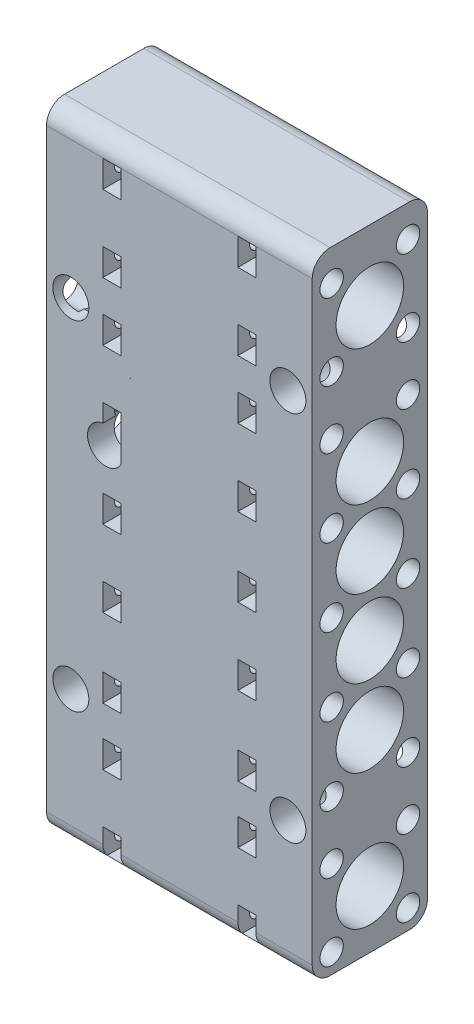
SolidWorks part; units mm, degrees
ref_plane "Plan de face" through (0, 0, 0) normal (0, 0, 1) x (1, 0, 0)
ref_plane "Plan de dessus" through (0, 0, 0) normal (0, 1, 0) x (1, 0, 0)
ref_plane "Plan de droite" through (0, 0, 0) normal (1, 0, 0) x (0, 0, -1)
sketch "Esquisse1" plane through (0, 0, 0) normal (0, 0, 1) x (1, 0, 0)
  line L0 (67.167, -107.583) -> (67.167, -12.4967) construction
  line L1 (67.167, -107.583) -> (118.268, -107.583) construction
  line L2 (67.167, -32.343) -> (118.6716, -32.343) construction
  line L3 (115.367, -14.0613) -> (67.167, -14.0613) construction
  line L4 (115.367, -108.723) -> (115.367, -10.1664) construction
  line L5 (108.4034, -26.123) -> (126.0173, -26.123) construction
  line L6 (91.267, -14.0613) -> (91.267, -17.6404) construction
  line L13 (56.607, -56.8666) -> (109.867, -56.8666) construction
  line L19 (91.267, 2.1061) -> (91.267, -137.8939) construction
  line L20 (61.767, 2.1061) -> (120.767, 2.1061)
  line L21 (61.767, 2.1061) -> (61.767, -137.8939)
  line L22 (61.767, -137.8939) -> (120.767, -137.8939)
  line L23 (120.767, 2.1061) -> (120.767, -137.8939)
  line L24 (61.767, -67.8939) -> (120.767, -67.8939) construction
  circle A0 centre (115.367, -108.723) radius 4
  circle A2 centre (115.367, -26.123) radius 4
  circle A3 centre (74.867, -56.8666) radius 4
  circle A6 centre (67.167, -107.583) radius 4
  circle A7 centre (67.167, -32.343) radius 4
  dimension "D14" = 140
  dimension "D2" = 75.24
  dimension "D3" = 48.2
  dimension "D4" = 6.22
  dimension "D5" = 0
  dimension "D6" = 1.14
  dimension "D15" = 59
extrude "Boss.-Extru.1" add sketch "Esquisse1" along normal blind 25.6
sketch "Esquisse2" plane through (120.767, 0, 0) normal (1, 0, 0) x (0, 0, -1)
  line L0 (-12.8, -125.0284) -> (-21.2853, -133.5136) construction
  line L1 (-12.8, -125.0284) -> (-12.8, -134.7242) construction
  line L2 (-12.8, -95.0284) -> (-21.2853, -103.6294) construction
  line L3 (-12.8, -137.8939) -> (-12.8, 2.1061) construction
  line L4 (-25.6, -137.8939) -> (0, -137.8939) construction
  line L5 (-25.6, 2.1061) -> (0, 2.1061) construction
  line L6 (-12.8, -95.0284) -> (-22.9445, -95.0284) construction
  line L7 (-21.2853, -86.4273) -> (-4.3147, -86.4273) construction
  line L8 (-21.2853, -69.2253) -> (-4.3147, -69.2253) construction
  line L9 (-21.2853, -52.0232) -> (-4.3147, -52.0232) construction
  line L10 (-12.8, -13.4222) -> (-21.2853, -4.9369) construction
  line L11 (-12.8, -125.0284) -> (-17.4685, -125.0284) construction
  line L12 (-12.8, -13.4222) -> (-17.4685, -13.4222) construction
  circle A0 centre (-12.8, -95.0284) radius 7.5
  circle A1 centre (-21.2853, -103.6294) radius 2.6
  circle A2 centre (-4.3147, -103.6294) radius 2.6
  circle A3 centre (-4.3147, -86.4273) radius 2.6
  circle A4 centre (-21.2853, -86.4273) radius 2.6
  circle A5 centre (-21.2853, -133.5136) radius 2.6
  circle A6 centre (-12.8, -125.0284) radius 7.5
  circle A7 centre (-4.3147, -133.5136) radius 2.6
  circle A8 centre (-4.3147, -69.2253) radius 2.6
  circle A9 centre (-21.2853, -69.2253) radius 2.6
  circle A10 centre (-12.8, -77.8263) radius 7.5
  circle A11 centre (-4.3147, -52.0232) radius 2.6
  circle A12 centre (-21.2853, -52.0232) radius 2.6
  circle A13 centre (-12.8, -60.6243) radius 7.5
  circle A14 centre (-4.3147, -34.8212) radius 2.6
  circle A15 centre (-21.2853, -34.8212) radius 2.6
  circle A16 centre (-12.8, -43.4222) radius 7.5
  circle A17 centre (-12.8, -13.4222) radius 7.5
  circle A18 centre (-21.2853, -4.9369) radius 2.6
  circle A19 centre (-4.3147, -4.9369) radius 2.6
  circle A20 centre (-4.3147, -116.5431) radius 2.6
  circle A21 centre (-21.2853, -116.5431) radius 2.6
  circle A22 centre (-4.3147, -21.9075) radius 2.6
  circle A23 centre (-21.2853, -21.9075) radius 2.6
  dimension "D1" = 30
  dimension "D2" = 30
extrude "Enlèv. mat.-Extru.1" cut sketch "Esquisse2" against normal blind 5
sketch "Esquisse3" plane through (120.767, 0, 0) normal (1, 0, 0) x (0, 0, -1)
  circle A0 centre (-12.8, -125.0284) radius 7.5
  circle A1 centre (-12.8, -95.0284) radius 7.5
  circle A2 centre (-12.8, -77.8263) radius 7.5
  circle A3 centre (-12.8, -60.6243) radius 7.5
  circle A4 centre (-12.8, -43.4222) radius 7.5
  circle A5 centre (-12.8, -13.4222) radius 7.5
extrude "Enlèv. mat.-Extru.2" cut sketch "Esquisse3" against normal blind 82
sketch "Esquisse4" plane through (61.767, 0, 0) normal (-1, 0, 0) x (0, 0, 1)
  line L0 (12.8, -13.4222) -> (21.2853, -4.9369) construction
  line L1 (12.8, -13.4222) -> (12.8, -125.0284) construction
  line L2 (12.8, -43.4222) -> (21.2853, -34.9369) construction
  line L3 (12.8, -43.4222) -> (23.3901, -43.4222) construction
  line L4 (12.8, -60.6243) -> (22.7072, -60.6243) construction
  line L5 (12.8, -77.8263) -> (22.0424, -77.8263) construction
  line L6 (12.8, -95.0284) -> (24.6, -95.0284) construction
  line L7 (12.8, -125.0284) -> (4.3147, -133.5136) construction
  line L8 (12.8, -13.4222) -> (17.9951, -13.4222) construction
  line L9 (12.8, -125.0284) -> (17.0426, -125.0284) construction
  circle A0 centre (21.2853, -4.9369) radius 2.6
  circle A1 centre (4.3147, -4.9369) radius 2.6
  circle A2 centre (21.2853, -34.9369) radius 2.6
  circle A3 centre (4.3147, -34.9369) radius 2.6
  circle A4 centre (4.3147, -51.9075) radius 2.6
  circle A5 centre (21.2853, -51.9075) radius 2.6
  circle A6 centre (4.3147, -69.341) radius 2.6
  circle A7 centre (21.2853, -69.341) radius 2.6
  circle A8 centre (4.3147, -86.3116) radius 2.6
  circle A9 centre (21.2853, -86.3116) radius 2.6
  circle A10 centre (4.3147, -103.7451) radius 2.6
  circle A11 centre (21.2853, -103.7451) radius 2.6
  circle A12 centre (4.3147, -133.5136) radius 2.6
  circle A13 centre (21.2853, -133.5136) radius 2.6
  circle A14 centre (4.3147, -21.9075) radius 2.6
  circle A15 centre (21.2853, -21.9075) radius 2.6
  circle A16 centre (4.3147, -116.5431) radius 2.6
  circle A17 centre (21.2853, -116.5431) radius 2.6
extrude "Enlèv. mat.-Extru.3" cut sketch "Esquisse4" against normal blind 5
ref_plane "Plan1" through (91.267, 0, 0) normal (-1, 0, 0) x (0, 0, 1)
sketch "Esquisse5" plane through (61.767, 0, 0) normal (-1, 0, 0) x (0, 0, 1)
  circle A0 centre (21.2853, -4.9369) radius 1.7
  circle A1 centre (21.2853, -21.9075) radius 1.7
  circle A2 centre (21.2853, -34.9369) radius 1.7
  circle A3 centre (21.2853, -51.9075) radius 1.7
  circle A4 centre (21.2853, -69.341) radius 1.7
  circle A5 centre (21.2853, -86.3116) radius 1.7
  circle A6 centre (21.2853, -103.7451) radius 1.7
  circle A7 centre (21.2853, -116.5431) radius 1.7
  circle A8 centre (21.2853, -133.5136) radius 1.7
  circle A9 centre (4.3147, -4.9369) radius 1.7
  circle A10 centre (4.3147, -21.9075) radius 1.7
  circle A11 centre (4.3147, -34.9369) radius 1.7
  circle A12 centre (4.3147, -51.9075) radius 1.7
  circle A13 centre (4.3147, -69.341) radius 1.7
  circle A14 centre (4.3147, -86.3116) radius 1.7
  circle A15 centre (4.3147, -103.7451) radius 1.7
  circle A16 centre (4.3147, -116.5431) radius 1.7
  circle A17 centre (4.3147, -133.5136) radius 1.7
extrude "Enlèv. mat.-Extru.4" cut sketch "Esquisse5" against normal blind 71
sketch "Esquisse6" plane through (91.267, 0, 0) normal (-1, 0, 0) x (0, 0, 1)
  line L0 (21.2853, -4.9369) -> (29.2853, -4.9369) construction
  line L1 (21.2853, -1.9369) -> (29.2853, -1.9369)
  line L2 (21.2853, -7.9369) -> (29.2853, -7.9369)
  arc A0 (21.2853, -1.9369) -> (21.2853, -7.9369) centre (21.2853, -4.9369) ccw
  arc A1 (29.2853, -7.9369) -> (29.2853, -1.9369) centre (29.2853, -4.9369) ccw
  point P3 (25.2853, -4.9369)
  line B0 (21.2853, -18.9075) -> (29.2853, -18.9075)
  arc B1 (29.2853, -24.9075) -> (29.2853, -18.9075) centre (29.2853, -21.9075) ccw
  line B2 (21.2853, -24.9075) -> (29.2853, -24.9075)
  arc B3 (21.2853, -18.9075) -> (21.2853, -24.9075) centre (21.2853, -21.9075) ccw
  line B4 (21.2853, -31.9369) -> (29.2853, -31.9369)
  arc B5 (29.2853, -37.9369) -> (29.2853, -31.9369) centre (29.2853, -34.9369) ccw
  line B6 (21.2853, -37.9369) -> (29.2853, -37.9369)
  arc B7 (21.2853, -31.9369) -> (21.2853, -37.9369) centre (21.2853, -34.9369) ccw
  line B8 (21.2853, -48.9075) -> (29.2853, -48.9075)
  arc B9 (29.2853, -54.9075) -> (29.2853, -48.9075) centre (29.2853, -51.9075) ccw
  line B10 (21.2853, -54.9075) -> (29.2853, -54.9075)
  arc B11 (21.2853, -48.9075) -> (21.2853, -54.9075) centre (21.2853, -51.9075) ccw
  line B12 (21.2853, -66.341) -> (29.2853, -66.341)
  arc B13 (29.2853, -72.341) -> (29.2853, -66.341) centre (29.2853, -69.341) ccw
  line B14 (21.2853, -72.341) -> (29.2853, -72.341)
  arc B15 (21.2853, -66.341) -> (21.2853, -72.341) centre (21.2853, -69.341) ccw
  line B16 (21.2853, -83.3116) -> (29.2853, -83.3116)
  arc B17 (29.2853, -89.3116) -> (29.2853, -83.3116) centre (29.2853, -86.3116) ccw
  line B18 (21.2853, -89.3116) -> (29.2853, -89.3116)
  arc B19 (21.2853, -83.3116) -> (21.2853, -89.3116) centre (21.2853, -86.3116) ccw
  line B20 (21.2853, -100.7451) -> (29.2853, -100.7451)
  arc B21 (29.2853, -106.7451) -> (29.2853, -100.7451) centre (29.2853, -103.7451) ccw
  line B22 (21.2853, -106.7451) -> (29.2853, -106.7451)
  arc B23 (21.2853, -100.7451) -> (21.2853, -106.7451) centre (21.2853, -103.7451) ccw
  line B24 (21.2853, -113.5431) -> (29.2853, -113.5431)
  arc B25 (29.2853, -119.5431) -> (29.2853, -113.5431) centre (29.2853, -116.5431) ccw
  line B26 (21.2853, -119.5431) -> (29.2853, -119.5431)
  arc B27 (21.2853, -113.5431) -> (21.2853, -119.5431) centre (21.2853, -116.5431) ccw
  line B28 (21.2853, -130.5136) -> (29.2853, -130.5136)
  arc B29 (29.2853, -136.5136) -> (29.2853, -130.5136) centre (29.2853, -133.5136) ccw
  line B30 (21.2853, -136.5136) -> (29.2853, -136.5136)
  arc B31 (21.2853, -130.5136) -> (21.2853, -136.5136) centre (21.2853, -133.5136) ccw
  line B32 (-3.6853, -1.9369) -> (4.3147, -1.9369)
  arc B33 (4.3147, -7.9369) -> (4.3147, -1.9369) centre (4.3147, -4.9369) ccw
  line B34 (-3.6853, -7.9369) -> (4.3147, -7.9369)
  arc B35 (-3.6853, -1.9369) -> (-3.6853, -7.9369) centre (-3.6853, -4.9369) ccw
  line B36 (-3.6853, -18.9075) -> (4.3147, -18.9075)
  arc B37 (4.3147, -24.9075) -> (4.3147, -18.9075) centre (4.3147, -21.9075) ccw
  line B38 (-3.6853, -24.9075) -> (4.3147, -24.9075)
  arc B39 (-3.6853, -18.9075) -> (-3.6853, -24.9075) centre (-3.6853, -21.9075) ccw
  line B40 (-3.6853, -31.9369) -> (4.3147, -31.9369)
  arc B41 (4.3147, -37.9369) -> (4.3147, -31.9369) centre (4.3147, -34.9369) ccw
  line B42 (-3.6853, -37.9369) -> (4.3147, -37.9369)
  arc B43 (-3.6853, -31.9369) -> (-3.6853, -37.9369) centre (-3.6853, -34.9369) ccw
  line B44 (-3.6853, -48.9075) -> (4.3147, -48.9075)
  arc B45 (4.3147, -54.9075) -> (4.3147, -48.9075) centre (4.3147, -51.9075) ccw
  line B46 (-3.6853, -54.9075) -> (4.3147, -54.9075)
  arc B47 (-3.6853, -48.9075) -> (-3.6853, -54.9075) centre (-3.6853, -51.9075) ccw
  line B48 (-3.6853, -66.341) -> (4.3147, -66.341)
  arc B49 (4.3147, -72.341) -> (4.3147, -66.341) centre (4.3147, -69.341) ccw
  line B50 (-3.6853, -72.341) -> (4.3147, -72.341)
  arc B51 (-3.6853, -66.341) -> (-3.6853, -72.341) centre (-3.6853, -69.341) ccw
  line B52 (-3.6853, -83.3116) -> (4.3147, -83.3116)
  arc B53 (4.3147, -89.3116) -> (4.3147, -83.3116) centre (4.3147, -86.3116) ccw
  line B54 (-3.6853, -89.3116) -> (4.3147, -89.3116)
  arc B55 (-3.6853, -83.3116) -> (-3.6853, -89.3116) centre (-3.6853, -86.3116) ccw
  line B56 (-3.6853, -100.7451) -> (4.3147, -100.7451)
  arc B57 (4.3147, -106.7451) -> (4.3147, -100.7451) centre (4.3147, -103.7451) ccw
  line B58 (-3.6853, -106.7451) -> (4.3147, -106.7451)
  arc B59 (-3.6853, -100.7451) -> (-3.6853, -106.7451) centre (-3.6853, -103.7451) ccw
  line B60 (-3.6853, -113.5431) -> (4.3147, -113.5431)
  arc B61 (4.3147, -119.5431) -> (4.3147, -113.5431) centre (4.3147, -116.5431) ccw
  line B62 (-3.6853, -119.5431) -> (4.3147, -119.5431)
  arc B63 (-3.6853, -113.5431) -> (-3.6853, -119.5431) centre (-3.6853, -116.5431) ccw
  line B64 (-3.6853, -130.5136) -> (4.3147, -130.5136)
  arc B65 (4.3147, -136.5136) -> (4.3147, -130.5136) centre (4.3147, -133.5136) ccw
  line B66 (-3.6853, -136.5136) -> (4.3147, -136.5136)
  arc B67 (-3.6853, -130.5136) -> (-3.6853, -136.5136) centre (-3.6853, -133.5136) ccw
sketch_block_instance "Bloc1-1"
sketch_block "Bloc1" parameters "D1"=2.825
sketch_block_instance "Bloc1-2"
sketch_block_instance "Bloc1-3"
sketch_block_instance "Bloc1-4"
sketch_block_instance "Bloc1-5"
sketch_block_instance "Bloc1-6"
sketch_block_instance "Bloc1-7"
sketch_block_instance "Bloc1-8"
sketch_block_instance "Bloc1-9"
sketch_block_instance "Bloc1-10"
sketch_block_instance "Bloc1-11"
sketch_block_instance "Bloc1-12"
sketch_block_instance "Bloc1-13"
sketch_block_instance "Bloc1-14"
sketch_block_instance "Bloc1-15"
sketch_block_instance "Bloc1-16"
sketch_block_instance "Bloc1-17"
extrude "Enlèv. mat.-Extru.5" cut sketch "Esquisse6" against normal blind 17 and the other way blind 17
sketch "Esquisse8" plane through (91.267, 0, 0) normal (-1, 0, 0) x (0, 0, 1)
  line L0 (25.6, -137.8939) -> (0, -137.8939) construction
  line L1 (0, 2.1061) -> (25.6, 2.1061)
  line L2 (0, 2.1061) -> (0, -137.8939)
  line L3 (0, -137.8939) -> (25.6, -137.8939)
  line L4 (25.6, 2.1061) -> (25.6, -137.8939)
extrude "Boss.-Extru.2" add sketch "Esquisse8" along normal blind 13 and the other way blind 13
sketch "Esquisse9" plane through (91.267, 0, 0) normal (-1, 0, 0) x (0, 0, 1)
  circle A0 centre (12.8, -125.0284) radius 7.5
  circle A1 centre (12.8, -95.0284) radius 7.5
  circle A2 centre (12.8, -77.8263) radius 7.5
  circle A3 centre (12.8, -60.6243) radius 7.5
  circle A4 centre (12.8, -43.4222) radius 7.5
  circle A5 centre (12.8, -13.4222) radius 7.5
  circle B0 centre (21.2853, -4.9369) radius 1.7
  circle B1 centre (21.2853, -21.9075) radius 1.7
  circle B2 centre (21.2853, -34.9369) radius 1.7
  circle B3 centre (21.2853, -51.9075) radius 1.7
  circle B4 centre (21.2853, -69.341) radius 1.7
  circle B5 centre (21.2853, -86.3116) radius 1.7
  circle B6 centre (21.2853, -103.7451) radius 1.7
  circle B7 centre (21.2853, -116.5431) radius 1.7
  circle B8 centre (21.2853, -133.5136) radius 1.7
  circle B9 centre (4.3147, -4.9369) radius 1.7
  circle B10 centre (4.3147, -21.9075) radius 1.7
  circle B11 centre (4.3147, -34.9369) radius 1.7
  circle B12 centre (4.3147, -51.9075) radius 1.7
  circle B13 centre (4.3147, -69.341) radius 1.7
  circle B14 centre (4.3147, -86.3116) radius 1.7
  circle B15 centre (4.3147, -103.7451) radius 1.7
  circle B16 centre (4.3147, -116.5431) radius 1.7
  circle B17 centre (4.3147, -133.5136) radius 1.7
sketch_block_instance "Bloc2-1"
sketch_block "Bloc2"
extrude "Enlèv. mat.-Extru.6" cut sketch "Esquisse9" against normal blind 33 and the other way blind 33
fillet "Congé1" radius 4 4 edges at (91.267, 2.1061, 0) (91.267, 2.1061, 25.6) (91.267, -137.8939, 0) (91.267, -137.8939, 25.6)
